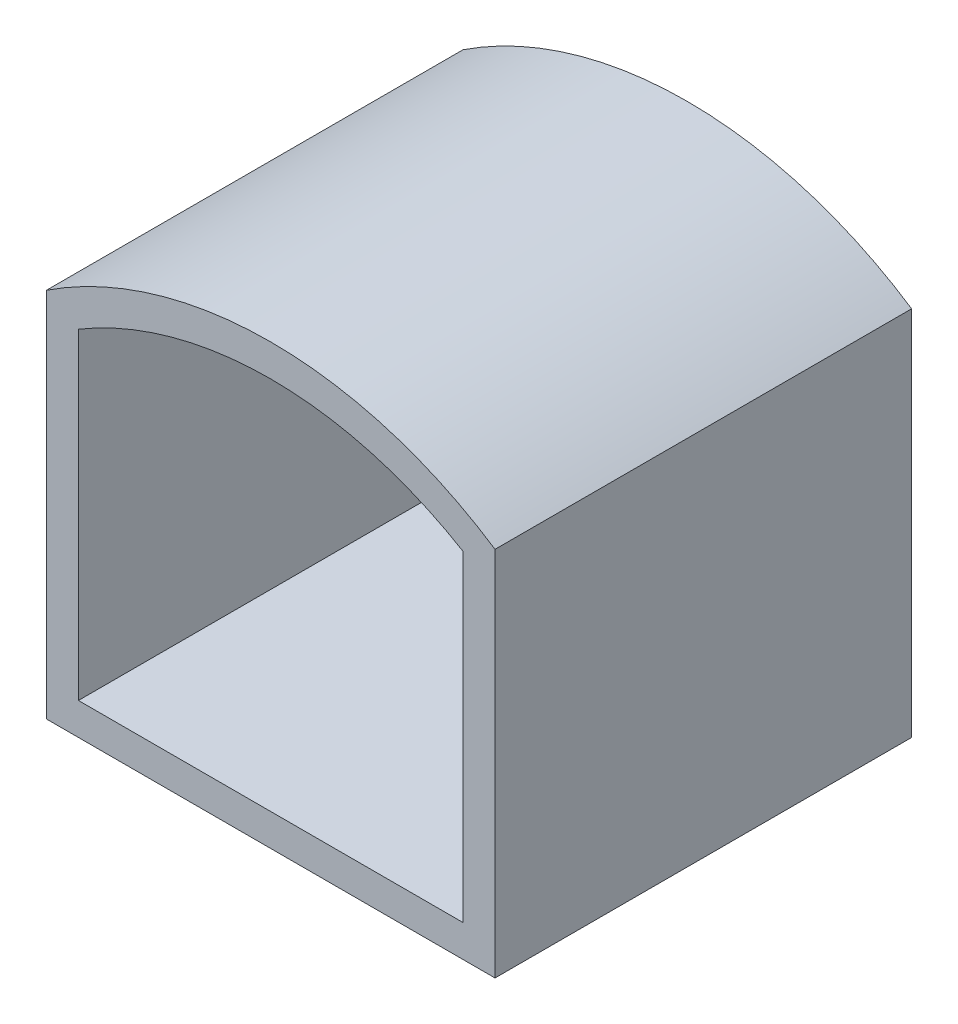
SolidWorks part; units mm, degrees
ref_plane "Front Plane" through (0, 0, 0) normal (0, 0, 1) x (1, 0, 0)
ref_plane "Top Plane" through (0, 0, 0) normal (0, 1, 0) x (1, 0, 0)
ref_plane "Right Plane" through (0, 0, 0) normal (1, 0, 0) x (0, 0, -1)
sketch "Sketch1" plane through (0, 0, 0) normal (0, 0, 1) x (1, 0, 0)
  line L5 (60, -50.165) -> (-60, -50.165)
  line L6 (60, -50.165) -> (60, 50.165)
  line L8 (-60, -50.165) -> (-60, 50.165)
  arc A0 (60, 50.165) -> (-60, 50.165) centre (0, -50.165) ccw
  point P5 (60, 0)
  dimension "D1" = 120
  dimension "D2" = 100.33
  dimension "D3" = 60
extrude "Boss-Extrude1" add sketch "Sketch1" along normal blind 120
shell "Shell1" thickness 10 removed face at (0, 4.143, 120) outward yes
